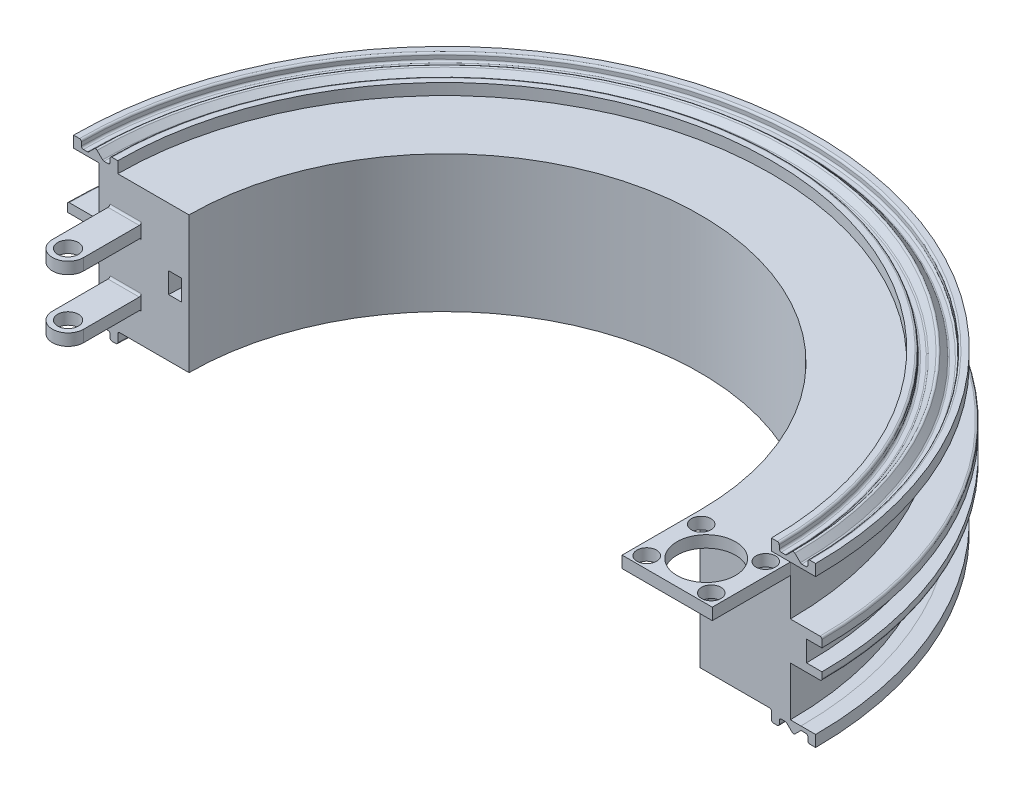
SolidWorks part; units mm, degrees
ref_plane "Front Plane" through (0, 0, 0) normal (0, 0, 1) x (1, 0, 0)
ref_plane "Top Plane" through (0, 0, 0) normal (0, 1, 0) x (1, 0, 0)
ref_plane "Right Plane" through (0, 0, 0) normal (1, 0, 0) x (0, 0, -1)
sketch "Sketch1" plane through (0, 0, 0) normal (0, 0, 1) x (1, 0, 0)
  line L0 (0, 22.1426) -> (0, -20.7935) construction
  line L1 (0, 22.1426) -> (0, -12.8574)
  line L12 (-27.2425, 1.8426) -> (-27.2449, 7.1426)
  line L14 (-31.1893, 7.1426) -> (-31.1893, 9.5187)
  line L23 (0, 4.6426) -> (-36.0381, 4.6426) construction
  line L25 (-5.2449, 7.1426) -> (-1.9449, 7.1426)
  line L26 (-5.2449, 7.1426) -> (-5.2449, 1.8426)
  line L27 (-5.2449, 1.8426) -> (-1.9449, 1.8426)
  line L28 (-1.9449, 7.1426) -> (-1.9449, 1.8426)
  line L29 (-22, 23.1426) -> (-23.9092, 25.0518)
  line L30 (-23.9092, 25.0518) -> (-25.8184, 23.1426)
  line L32 (-25.8184, 22.1426) -> (-23.0909, 22.1426)
  line L33 (-23.0909, 22.1426) -> (-23.0909, 9.5187)
  line L34 (-23.0909, 9.5187) -> (-31.1893, 9.5187)
  line L35 (-31.1893, -0.2335) -> (-23.0909, -0.2335)
  line L42 (-31.1893, -0.2335) -> (-31.1893, 1.8426)
  line L43 (-31.1893, 1.8426) -> (-27.2425, 1.8426)
  line L44 (-31.1893, 7.1426) -> (-27.2449, 7.1426)
  line L45 (-22, 23.1426) -> (-20.25, 23.1426)
  line L46 (-20.25, 23.1426) -> (-20.25, 25.0518)
  line L47 (-18.25, 25.0518) -> (-18.25, 22.1426)
  line L48 (-18.25, 22.1426) -> (0, 22.1426)
  line L49 (-20.25, 25.0518) -> (-18.25, 25.0518)
  line L50 (-25.8184, 23.1426) -> (-27.5684, 23.1426)
  line L51 (-27.5684, 23.1426) -> (-27.5684, 25.0518)
  line L52 (-27.5684, 25.0518) -> (-29.5684, 25.0518)
  line L53 (-29.5684, 25.0518) -> (-29.5684, 22.1426)
  line L54 (-29.5684, 22.1426) -> (-25.8184, 22.1426)
  line L65 (-29.5684, -12.8574) -> (-25.8184, -12.8574)
  line L66 (-29.5684, -15.7666) -> (-29.5684, -12.8574)
  line L67 (-27.5684, -15.7666) -> (-29.5684, -15.7666)
  line L68 (-27.5684, -13.8574) -> (-27.5684, -15.7666)
  line L69 (-25.8184, -13.8574) -> (-27.5684, -13.8574)
  line L70 (-20.25, -15.7666) -> (-18.25, -15.7666)
  line L71 (-18.25, -12.8574) -> (0, -12.8574)
  line L72 (-18.25, -15.7666) -> (-18.25, -12.8574)
  line L73 (-20.25, -13.8574) -> (-20.25, -15.7666)
  line L74 (-22, -13.8574) -> (-20.25, -13.8574)
  line L75 (-23.0909, -12.8574) -> (-23.0909, -0.2335)
  line L76 (-25.8184, -12.8574) -> (-23.0909, -12.8574)
  line L77 (-23.9092, -15.7666) -> (-25.8184, -13.8574)
  line L78 (-22, -13.8574) -> (-23.9092, -15.7666)
  dimension "D1" = 35
  dimension "D2" = 1.75
  dimension "D3" = 1
  dimension "D4" = 2.7
  dimension "D5" = 2.7
  dimension "D6" = 2
  dimension "D7" = 2
  dimension "D8" = 5.3
  dimension "D10" = 5.3
  dimension "D11" = 3.3
  dimension "D12" = 22
sketch "Sketch3" plane through (0, 0, 0) normal (0, 1, 0) x (1, 0, 0)
  arc A0 (0, 0) -> (130.92, 0) centre (65.46, 0) cw
sweep "Sweep3" add profiles "Sketch1" path "Sketch3"
sketch "Sketch13" plane through (0, 0, 0) normal (0, 0, 1) x (1, 0, 0)
  line L4 (-5.2449, 4.4926) -> (-5.2449, 18.9333) construction
  line L5 (-5.2449, 1.8426) -> (-5.2449, 7.1426) construction
  line L6 (-5.2449, 18.9333) -> (-5.2449, -5.0069) construction
  line L9 (-16.2449, 7.1426) -> (-16.2449, 2.1426) construction
  line L11 (-20.2449, 10.9426) -> (-16.2312, 10.9426)
  line L12 (-12.2449, 10.9426) -> (-12.2449, 13.9426)
  line L13 (-20.2449, 10.9426) -> (-20.2449, 13.9426)
  line L14 (-20.2449, 13.9426) -> (-12.2449, 13.9426)
  line L17 (-20.2449, -1.9574) -> (-20.2449, -4.9574)
  line L18 (-20.2449, -4.9574) -> (-12.2449, -4.9574)
  line L19 (-12.2449, -1.9574) -> (-12.2449, -4.9574)
  line L20 (-20.2449, -1.9574) -> (-12.2449, -1.9574)
  line L21 (-16.2312, 10.9426) -> (-12.2449, 10.9426)
  dimension "D1" = 8
  dimension "D2" = 4
  dimension "D3" = 3
  dimension "D4" = 12.9
extrude "Boss-Extrude1" add sketch "Sketch13" along normal blind 1 contours L14 L13 L12 | L20 L17 L18 L19 region at (-16.2449, 12.4426, 0) region at (-16.2449, -3.4574, 0)
sketch "Sketch15" plane through (0, 13.9426, 0) normal (0, 1, 0) x (1, 0, 0)
  line L0 (-20.2449, -14.7441) -> (-20.2449, -1)
  line L1 (-20.2449, 0) -> (-20.2449, -14.7441) construction
  line L2 (-12.2449, 0) -> (-12.2449, -14.7441) construction
  line L3 (-20.2449, -14.7441) -> (-12.2449, -14.7441) construction
  line L4 (-12.2449, -14.7441) -> (-12.2449, -1)
  circle A0 centre (-16.2449, -14.7441) radius 2.65
  circle A1 centre (-16.2449, -14.7441) radius 4
  line M8 (-20.2449, -1) -> (-12.2449, -1)
  dimension "D1" = 5.3
extrude "Boss-Extrude4" add sketch "Sketch15" against normal blind 3 contours A1 A0 | A1 L4 L0 M8 region at (-16.2449, 13.9426, 6.3388) region at (-16.2449, 13.9426, 10.8572)
ref_plane "Plane3" through (0, 4.4926, 0) normal (0, 1, 0) x (1, 0, 0)
mirror "Mirror3" about plane through (0, 4.4926, 0) normal (0, 1, 0) of "Boss-Extrude4", "Boss-Extrude1"
sketch "Sketch17" plane through (0, 0, 0) normal (0, 0, 1) x (1, 0, 0)
  line L5 (130.92, 22.1426) -> (154.0109, 22.1426)
  line L6 (154.0109, 22.1426) -> (154.0109, 19.1426)
  line L7 (154.0109, 22.1426) -> (154.0109, 9.5187) construction
  line L8 (154.0109, 19.1426) -> (130.92, 19.1426)
  line L9 (130.92, -12.8574) -> (130.92, 22.1426) construction
  line L10 (130.92, 19.1426) -> (130.92, 22.1426)
  dimension "D1" = 3
extrude "Boss-Extrude5" add sketch "Sketch17" along normal blind 20
sketch "Sketch18" plane through (0, 19.1426, 0) normal (0, -1, 0) x (1, 0, 0)
  line L0 (142.4654, 20) -> (142.4654, 0) construction
  line L1 (130.92, 20) -> (154.0109, 20) construction
  line L2 (130.92, 0) -> (154.0109, 0) construction
  line L3 (130.92, 10) -> (154.0109, 10) construction
  line L4 (130.92, 20) -> (130.92, 0) construction
  line L5 (154.0109, 20) -> (154.0109, 0) construction
  circle A0 centre (142.4654, 10) radius 7.5
  circle A1 centre (134.2018, 16.9741) radius 2.5
  circle A2 centre (150.729, 16.9741) radius 2.5
  circle A3 centre (134.2018, 3.0259) radius 2.5
  circle A4 centre (150.729, 3.0259) radius 2.5
extrude "Cut-Extrude1" cut sketch "Sketch18" against normal blind 4
fillet "Fillet1" radius 0.5 1 edges at (65.46, 25.0518, -89.3692)
fillet "Fillet2" radius 0.5 1 edges at (65.46, 23.1426, -91.2784)
fillet "Fillet3" radius 0.5 1 edges at (65.46, 23.1426, -93.0284)
fillet "Fillet4" radius 0.5 2 edges at (65.46, 23.1426, -85.71) (65.46, 23.1426, -87.46)
fillet "Fillet5" radius 0.5 3 edges at (65.46, -15.7666, -85.71) (65.46, -13.8574, -87.46) (65.46, -15.7666, -89.3692)
fillet "Fillet6" radius 0.5 3 edges at (65.46, -12.8574, -83.71) (65.46, -15.7666, -83.71) (65.46, -13.8574, -85.71)
fillet "Fillet7" radius 0.5 3 edges at (65.46, -13.8574, -91.2784) (65.46, -15.7666, -93.0284) (65.46, -13.8574, -93.0284)
fillet "Fillet8" radius 0.5 4 edges at (-16.2449, 13.9426, 0) (-16.2449, -4.9574, 0) (-16.2449, 10.9426, 0) (-16.2449, -1.9574, 0)
fillet "Fillet9" radius 0.5 2 edges at (65.46, -0.2335, -96.6492) (65.46, 9.5187, -96.6492)
fillet "Fillet10" radius 0.5 2 edges at (65.46, 25.0518, -93.0284) (65.46, 25.0518, -85.71)
